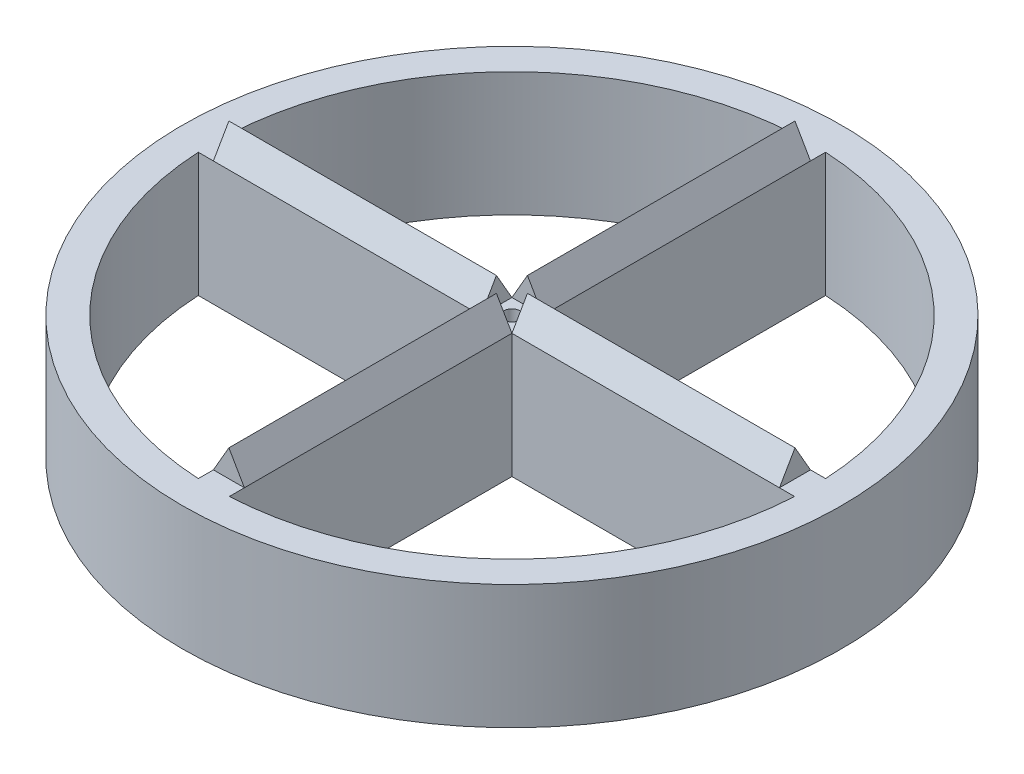
SolidWorks part; units mm, degrees
ref_plane "Front Plane" through (0, 0, 0) normal (0, 0, 1) x (1, 0, 0)
ref_plane "Top Plane" through (0, 0, 0) normal (0, 1, 0) x (1, 0, 0)
ref_plane "Right Plane" through (0, 0, 0) normal (1, 0, 0) x (0, 0, -1)
sketch "Sketch1" plane through (0, 0, 0) normal (0, 1, 0) x (1, 0, 0)
  line L2 (-5, 5) -> (-5, 96.12)
  line L3 (5, 5) -> (5, 96.12)
  line L4 (-5, -5) -> (-5, -96.12)
  line L5 (5, -5) -> (5, -96.12)
  line L8 (-5, 5) -> (-96.12, 5)
  line L9 (5, 5) -> (96.12, 5)
  line L10 (-5, -5) -> (-96.12, -5)
  line L11 (5, -5) -> (96.12, -5)
  circle A0 centre (0, 0) radius 106.25
  arc A1 (96.12, 5) -> (5, 96.12) centre (0, 0) ccw
  arc A2 (-5, 96.12) -> (-96.12, 5) centre (0, 0) ccw
  arc A3 (-96.12, -5) -> (-5, -96.12) centre (0, 0) ccw
  arc A4 (5, -96.12) -> (96.12, -5) centre (0, 0) ccw
extrude "Boss-Extrude1" add sketch "Sketch1" along normal blind 40
sketch "Sketch2" plane through (-5, 0, 0) normal (-1, 0, 0) x (0, 0, 1)
  line L0 (-5, 40) -> (5, 40)
  line L1 (-5, 40) -> (-96.12, 40) construction
  line L2 (96.12, 40) -> (5, 40) construction
  line L3 (5, 40) -> (0, 48.6603)
  line L4 (-5, 40) -> (0, 48.6603)
extrude "Boss-Extrude2" add sketch "Sketch2" along normal blind 86.25 and the other way blind 96.25
sketch "Sketch5" plane through (0, 0, -5) normal (0, 0, -1) x (-1, 0, 0)
  line L0 (5, 57.6602) -> (-5, 57.6602)
  line L2 (-5, 57.6602) -> (-5, 40)
  line L4 (5, 57.6602) -> (5, 40)
  line L5 (5, 40) -> (-5, 40)
  line L6 (106.25, 40) -> (-106.25, 40) construction
extrude "Cut-Extrude3" cut sketch "Sketch5" against normal blind 96.25 and the other way blind 96.25
sketch "Sketch6" plane through (0, 0, -5) normal (0, 0, -1) x (-1, 0, 0)
  line L0 (5, 40) -> (-5, 40)
  line L1 (-5, 40) -> (0, 48.6603)
  line L2 (5, 40) -> (0, 48.6603)
extrude "Boss-Extrude3" add sketch "Sketch6" along normal blind 86.25 and the other way blind 96.25
sketch "Sketch7" plane through (-5, 0, 0) normal (-1, 0, 0) x (0, 0, 1)
  line L0 (-5, 40) -> (-5, 55.5089)
  line L1 (-5, 40) -> (-91.25, 40) construction
  line L2 (-5, 55.5089) -> (5, 55.5089)
  line L3 (-5, 40) -> (5, 40)
  line L4 (91.25, 40) -> (5, 40) construction
  line L5 (106.25, 40) -> (-106.25, 40) construction
  line L6 (5, 40) -> (5, 55.5089)
extrude "Cut-Extrude4" cut sketch "Sketch7" against normal blind 10
sketch "Sketch8" plane through (0, 40, 0) normal (0, 1, 0) x (1, 0, 0)
  circle A0 centre (0, 0) radius 2.6
extrude "Cut-Extrude5" cut sketch "Sketch8" against normal blind 110
